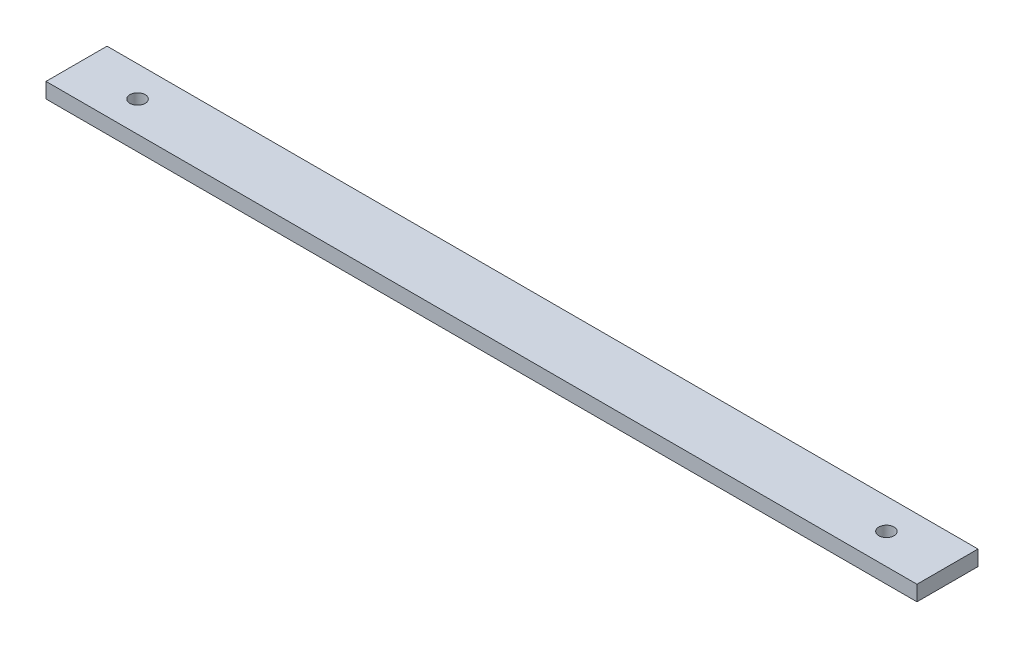
SolidWorks part; units mm, degrees
material "6061 Alloy"
ref_plane "Front Plane" through (0, 0, 0) normal (0, 0, 1) x (1, 0, 0)
ref_plane "Top Plane" through (0, 0, 0) normal (0, 1, 0) x (1, 0, 0)
ref_plane "Right Plane" through (0, 0, 0) normal (1, 0, 0) x (0, 0, -1)
sketch "Sketch1" plane through (0, 0, 0) normal (0, 1, 0) x (1, 0, 0)
  line L1 (0, 0) -> (362.4456, 0)
  line L2 (0, 0) -> (0, -25.4)
  line L3 (0, -25.4) -> (362.4456, -25.4)
  line L4 (362.4456, 0) -> (362.4456, -25.4)
  dimension "D1" = 362.4456
  dimension "D2" = 25.4
extrude "Boss-Extrude1" add sketch "Sketch1" along normal blind 6.35
sketch "Sketch2" plane through (0, 0, 0) normal (0, -1, 0) x (1, 0, 0)
  line L0 (0, 0) -> (0, 25.4) construction
  line L1 (362.4456, 0) -> (0, 0) construction
  circle A0 centre (25.4, 12.7) radius 3.175
  circle A1 centre (337.0456, 12.7) radius 3.175
  dimension "D1" = 6.35
  dimension "D2" = 25.4
  dimension "D4" = 311.6456
  dimension "D5" = 6.35
  dimension "D6" = 12.7
  dimension "D3" = 12.7
extrude "Cut-Extrude1" cut sketch "Sketch2" against normal up to next
